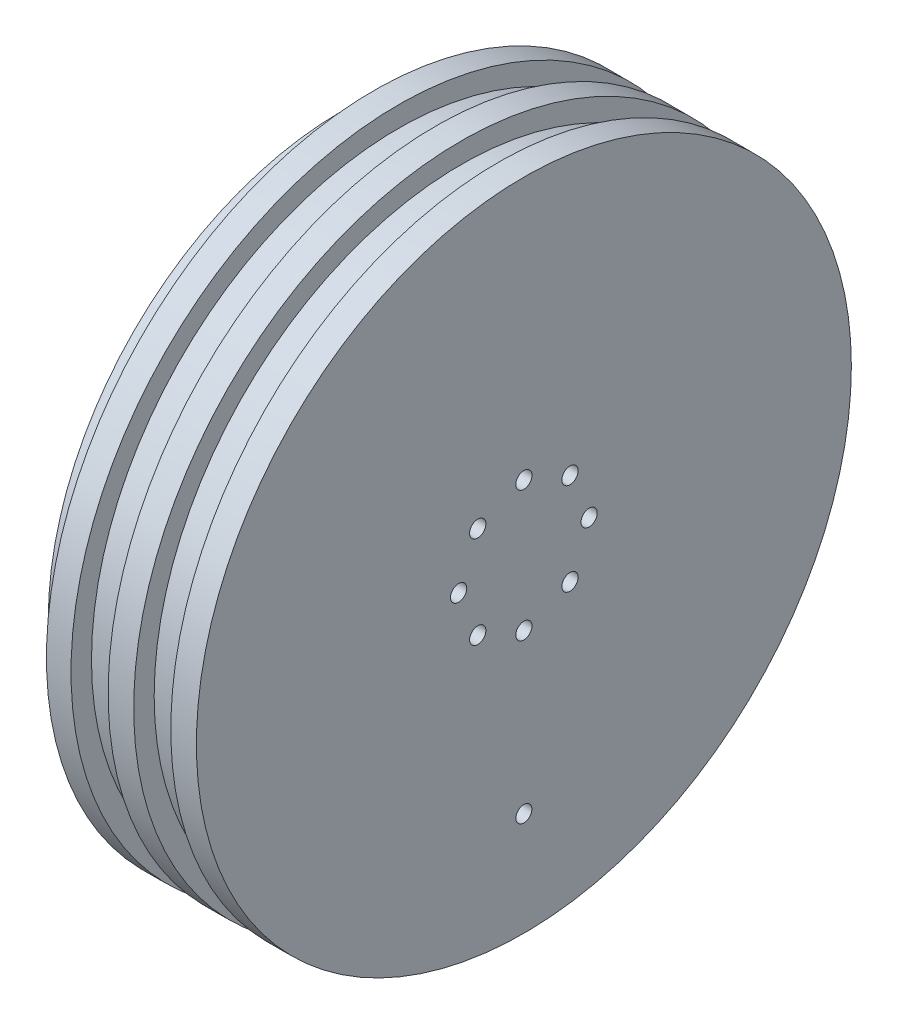
SolidWorks part; units mm, degrees
note: '?' marks a value the reader was unsure of.
material "6061 Alloy"
ref_plane "Front Plane" through (0, 0, 0) normal (0, 0, 1) x (1, 0, 0)
ref_plane "Top Plane" through (0, 0, 0) normal (0, 1, 0) x (1, 0, 0)
ref_plane "Right Plane" through (0, 0, 0) normal (1, 0, 0) x (0, 0, -1)
ref_axis "Axis1" through (17.7799, 0, 0) along (-1, 0, 0)
sketch "Sketch1" plane through (0, 0, 0) normal (0, 0, 1) x (1, 0, 0)
  line L0 (0, -32.512) -> (0, 32.512)
  line L1 (0, 32.512) -> (-2.54, 32.512)
  line L2 (-2.54, 32.512) -> (-2.54, 30.48)
  line L3 (-2.54, 30.48) -> (-6.223, 30.48)
  line L4 (-6.223, 30.48) -> (-6.223, 32.512)
  line L5 (-6.223, 32.512) -> (-8.763, 32.512)
  line L6 (-8.763, 32.512) -> (-8.763, 30.48)
  line L7 (-8.763, 30.48) -> (-12.446, 30.48)
  line L8 (-12.446, 30.48) -> (-12.446, 32.512)
  line L9 (-12.446, 32.512) -> (-14.885, 32.512)
  line L12 (-18.06, 29.1592) -> (-18.06, 4.7625)
  line L13 (-12.599, 0) -> (0, 0)
  line L17 (-12.446, -30.48) -> (-12.446, -32.512)
  line L18 (-8.763, -30.48) -> (-12.446, -30.48)
  line L19 (-8.763, -32.512) -> (-8.763, -30.48)
  line L20 (-6.223, -32.512) -> (-8.763, -32.512)
  line L21 (-6.223, -30.48) -> (-6.223, -32.512)
  line L22 (-2.54, -30.48) -> (-6.223, -30.48)
  line L23 (-2.54, -32.512) -> (-2.54, -30.48)
  line L24 (0, -32.512) -> (-2.54, -32.512)
  line L25 (-18.06, 4.7625) -> (-12.599, 4.7625)
  line L26 (-12.599, 4.7625) -> (-12.599, 0)
  line L27 (-12.599, 0) -> (-12.599, -4.7625)
  line L28 (-12.599, -4.7625) -> (-18.06, -4.7625)
  line L29 (-18.06, -4.7625) -> (-18.06, -29.1592)
  line L30 (-18.06, 4.7625) -> (-18.06, -4.7625) construction
  line L31 (-14.885, 32.512) -> (-14.885, 29.1592)
  line L32 (-14.885, 29.1592) -> (-18.06, 29.1592)
  dimension "D1" = 65.024
  dimension "D2" = 3.683
  dimension "D3" = 2.032
  dimension "D4" = 2.54
  dimension "D5" = 58.3184
  dimension "D7" = 18.06
  dimension "D8" = 2.54
  dimension "D9" = 9.525
  dimension "D10" = 5.461
  dimension "D11" = 3.175
revolve "Revolve1" add sketch "Sketch1" angle 360 about axis through (17.7799, 0, 0) along (-1, 0, 0)
chamfer "Chamfer2" [suppressed] distance 0.254 angle 45
sketch "Sketch22" plane through (-18.06, 0, 0) normal (-1, 0, 0) x (0, 0, 1)
  line L0 (0, 0) -> (0, 20.6375) construction
  circle A0 centre (0, 0) radius 20.6375 construction
  point P5 (0, 20.6375)
  dimension "D1" = 41.275
hole_wizard "#20 (0.161) Diameter Hole1" positions "Sketch23" profile "Sketch24" hole size "#20" standard "ANSI Inch"
sketch "Sketch23" plane through (-18.06, 0, 0) normal (-1, 0, 0) x (0, 0, 1)
  point P0 (0, 20.6375)
sketch "Sketch24" plane through (-18.06, 20.6375, 0) normal (0, 1, 0) x (0, 0, 1)
  line L0 (0, 0) -> (0, 10.8806)
  line L1 (0, 10.8806) -> (2.0447, 9.652)
  line L2 (2.0447, 9.652) -> (2.0447, 0)
  line L5 (2.0447, 0) -> (0, 0)
  line L10 (0, 10.8806) -> (-2.0447, 9.652) construction
  line L11 (0, -6.35) -> (0, 107.95) construction
  dimension "Hole Dia." = 4.0894
  dimension "Hole Depth" = 9.652
  dimension "Drill Angle" = 118
pattern_circular "CirPattern2" count 3 over 360 about axis through (0, 0, 0) along (1, 0, 0) of "#20 (0.161) Diameter Hole1"
ref_plane "Top of Part" through (0, 0, 0) normal (1, 0, 0) x (0, 0, -1)
ref_axis "Axis2" through (0, -42.1217, 0) along (0, 1, 0)?
ref_axis "Axis3" through (-26.67, 0, 0) along (1, 0, 0)?
ref_plane "Plane3" through (0, 0, 0) normal (0, -0.5, 0.866) x (1, 0, 0)
ref_axis "Axis4" through (0, -1.4216, -0.8207) along (0, 0.866, 0.5)?
ref_plane "Plane7" through (0, 0, 0) normal (0.9877, -0.0782, 0.1355) x (0, 0.866, 0.5)
sketch "Sketch7" plane through (0, 0, 0) normal (1, 0, 0) x (0, 0, -1)
  line L0 (0, 0) -> (0, 6.477) construction
  line L1 (0, 0) -> (3.2385, 5.6092) construction
  line L2 (0, 0) -> (6.477, 0) construction
  line L3 (0, 0) -> (3.2385, -5.6092) construction
  line L4 (0, 0) -> (-3.2385, -5.6092) construction
  line L5 (0, 0) -> (-6.477, 0) construction
  line L7 (0, 0) -> (-3.2385, 5.6092) construction
  circle A0 centre (0, 0) radius 6.477 construction
  point P12 (0, 0)
  point P13 (0, 0)
  dimension "D2" = 12.954
  dimension "D3" = 30
  dimension "D1" = 6
sketch "Sketch17" plane through (0, 0, 0) normal (0.9877, -0.0782, 0.1355) x (0, 0.866, 0.5)
  point P0 (-3.2385, -5.5402)
hole_wizard "Ø1.5 (1.5) Diameter Hole4" [suppressed] positions "Sketch18" profile "Sketch19" hole size "Ø1.5" standard "ANSI Metric"
sketch "Sketch18" plane through (0, 0, 0) normal (0.9877, -0.0782, 0.1355) x (0, 0.866, 0.5)
  point P0 (-3.2385, -5.5402)
sketch "Sketch19" plane through (0.8667, -0.0686, -6.3581) normal (-0.041, 0.7065, 0.7065) x (0.151, 0.7034, -0.6946)
  line L0 (0, 0) -> (0, 24.5196)
  line L1 (0, 24.5196) -> (0.75, 24.069)
  line L2 (0.75, 24.069) -> (0.75, 0)
  line L5 (0.75, 0) -> (0, 0)
  line L10 (0, 24.5196) -> (-0.75, 24.069) construction
  line L11 (0, -6.35) -> (0, 107.95) construction
  dimension "Hole Dia." = 1.5
  dimension "Hole Depth" = 24.069
  dimension "Drill Angle" = 118
ref_plane "Plane8" [suppressed] through (0, 0, 0) normal (1, 0, 0) x (0, 0, -1)
pattern_circular "CirPattern1" [suppressed] count 6 over 360 about axis through (-26.67, 0, 0) along (1, 0, 0)
ref_axis "Axis7" [suppressed] through (-9.5533, 6.3658, 4.5489) along (0.9877, -0.0782, -0.1355)?
ref_axis "Axis8" [suppressed] through (-9.622, 7.1332, -3.2385) along (0.9877, -0.1564, 0)?
ref_axis "Axis9" [suppressed] through (-10.3183, 0.8171, -7.8923) along (0.9877, -0.0782, 0.1355)?
ref_axis "Axis10" [suppressed] through (-9.0092, -6.3227, -4.4742) along (0.9877, 0.0782, 0.1355)?
ref_axis "Axis11" [suppressed] through (-10.5844, -7.2856, 3.2385) along (0.9877, 0.1564, 0)?
ref_axis "Axis12" [suppressed] through (-9.8881, -0.7831, 7.8333) along (0.9877, 0.0782, -0.1355)?
sketch "Sketch20" [suppressed] plane through (0, 0, 0) normal (1, 0, 0) x (0, 0, -1)
  ellipse E0 centre (-6.477, 0) end of major axis (-5.8194, 0.3797) minor radius 0.75 construction
  point P0 (-7.234, -0.0132)
sketch "Sketch21" [suppressed] plane through (-18.06, 0, 0) normal (-1, 0, 0) x (0, 0, 1)
  ellipse E0 centre (8.9542, -1.4302) end of major axis (8.2966, -1.0505) minor radius 0.75 construction
  point P0 (9.7079, -1.3677)
hole_wizard "Ø1.5mm Dowel Hole1" [suppressed] positions "Sketch36" profile "Sketch37" hole size "Ø1.5" standard "ANSI Metric"
sketch "Sketch36" [suppressed] plane through (0, 0, 0) normal (1, 0, 0) x (0, 0, -1)
  point P0 (0, 0)
sketch "Sketch37" [suppressed] plane through (0, 0, 0) normal (0, 1, 0) x (0, 0, -1)
  line L0 (0, 0) -> (0, 25.4)
  line L1 (0, 25.4) -> (0.75, 25.4)
  line L2 (0.75, 25.4) -> (0.75, 0)
  line L5 (0.75, 0) -> (0, 0)
  line L11 (0, -6.35) -> (0, 107.95) construction
  dimension "Thru Hole Dia." = 1.5
  dimension "Thru Hole Depth" = 25.4
hole_wizard "#8-32 Tapped Hole1" [suppressed] positions "Sketch40" profile "Sketch41" tap size "#8-32" standard "ANSI Inch"
sketch "Sketch40" plane through (-12.599, 0, 0) normal (-1, 0, 0) x (0, 0, 1)
  point P0 (0, 0)
sketch "Sketch41" plane through (-12.599, 0, 0) normal (0, 1, 0) x (0, 0, 1)
  line L0 (0, 0) -> (0, 7.3878)
  line L1 (0, 7.3878) -> (1.7272, 6.35)
  line L2 (1.7272, 6.35) -> (1.7272, 0)
  line L5 (1.7272, 0) -> (0, 0)
  line L10 (0, 7.3878) -> (-1.7272, 6.35) construction
  line L11 (0, -6.35) -> (0, 107.95) construction
  dimension "Tap Drill Dia." = 3.4544
  dimension "Tap Drill Depth" = 6.35
  dimension "Drill Angle" = 118
cosmetic thread "Hole Thread3" [suppressed] parameters "D1"=6.35, "D2"=4.1656
sketch "Sketch43" plane through (-18.06, 0, 0) normal (-1, 0, 0) x (0, 0, 1)
  line L0 (0, 0) -> (0, 20.6375) construction
  line L1 (0, 20.6375) -> (17.8726, -10.3188) construction
  line L2 (17.8726, -10.3188) -> (0, 0) construction
  line L3 (0, 0) -> (17.8726, 10.3187) construction
  circle A0 centre (0, 0) radius 20.6375 construction
  point P8 (8.9363, 5.1594)
  dimension "D1" = 41.275
hole_wizard "#50 (0.07) Diameter Hole1" positions "Sketch44" profile "Sketch45" hole size "#50" standard "ANSI Inch"
sketch "Sketch44" plane through (-18.06, 0, 0) normal (-1, 0, 0) x (0, 0, 1)
  point P0 (17.8726, 10.3187)
sketch "Sketch45" plane through (-18.06, 10.3187, 17.8726) normal (0, 1, 0) x (0, 0, 1)
  line L0 (0, 0) -> (0, 12.4722)
  line L1 (0, 12.4722) -> (0.889, 11.938)
  line L2 (0.889, 11.938) -> (0.889, 0)
  line L5 (0.889, 0) -> (0, 0)
  line L10 (0, 12.4722) -> (-0.889, 11.938) construction
  line L11 (0, -6.35) -> (0, 107.95) construction
  dimension "Hole Dia." = 1.778
  dimension "Hole Depth" = 11.938
  dimension "Drill Angle" = 118
sketch "Sketch46" plane through (0, 0, 0) normal (1, 0, 0) x (0, 0, -1)
  line L0 (0, 0) -> (-17.8726, -10.3188) construction
  line L1 (-17.8726, -10.3188) -> (17.8726, -10.3187) construction
  line L2 (17.8726, -10.3187) -> (0, 0) construction
  line L3 (0, 0) -> (0, -22.225) construction
  circle A0 centre (0, 0) radius 22.225 construction
  point P3 (0, -10.3188)
  dimension "D1" = 44.45
sketch "Sketch60" plane through (-12.599, 0, 0) normal (-1, 0, 0) x (0, 0, 1)
  circle A0 centre (0, 0) radius 4.7625
extrude "Boss-Extrude4" add sketch "Sketch60" along normal up to surface (5.461 mm away) up to face at (-18.06, 10.3187, 18.7616)
sketch "Sketch54" plane through (0, 0, 0) normal (1, 0, 0) x (0, 0, -1)
  circle A1 centre (0, 6.477) radius 0.8065
  circle A2 centre (4.5799, 4.5799) radius 0.8065
  circle A3 centre (6.477, 0) radius 0.8065
  circle A4 centre (4.5799, -4.5799) radius 0.8065
  circle A5 centre (0, -6.477) radius 0.8065
  circle A6 centre (-4.5799, -4.5799) radius 0.8065
  circle A7 centre (-6.477, 0) radius 0.8065
  circle A8 centre (-4.5799, 4.5799) radius 0.8065
  circle A9 centre (0, 0) radius 6.477 construction
  point P14 (0, 0)
  dimension "D3" = 8
extrude "Cut-Extrude1" cut sketch "Sketch54" against normal up to surface (18.06 mm away)
hole_wizard "1/16 (0.0625) Diameter Hole1" positions "3DSketch4" profile "Sketch63" hole size "1/16" standard "ANSI Inch" end condition through all
sketch3d "3DSketch4"
  point P0 (0, -22.225, 0)
  point P3 (0, -22.225, 0)
sketch "Sketch63" plane through (0, -22.225, 0) normal (0, 1, 0) x (0, 0, -1)
  line L0 (0, 0) -> (0, 18.06)
  line L1 (0, 18.06) -> (0.7937, 18.06)
  line L2 (0.7937, 18.06) -> (0.7937, 0)
  line L5 (0.7937, 0) -> (0, 0)
  line L11 (0, -6.35) -> (0, 107.95) construction
  dimension "Thru Hole Dia." = 1.5875
  dimension "Thru Hole Depth" = 18.06
hole_wizard "Q (0.332) Diameter Hole2" positions "3DSketch7" profile "Sketch67" hole size "Q" standard "ANSI Inch"
sketch3d "3DSketch7"
  line L0 (-18.06, -22.225, 0) -> (0, -22.225, 0) construction
  point P0 (-18.06, -22.225, 0)
sketch "Sketch67" plane through (-18.06, -22.225, 0) normal (0, 1, 0) x (0, 0, 1)
  line L0 (0, 0) -> (0, 11.4235)
  line L1 (0, 11.4235) -> (4.2164, 8.89)
  line L2 (4.2164, 8.89) -> (4.2164, 0)
  line L5 (4.2164, 0) -> (0, 0)
  line L10 (0, 11.4235) -> (-4.2164, 8.89) construction
  line L11 (0, -6.35) -> (0, 107.95) construction
  dimension "Hole Dia." = 8.4328
  dimension "Hole Depth" = 8.89
  dimension "Drill Angle" = 118
